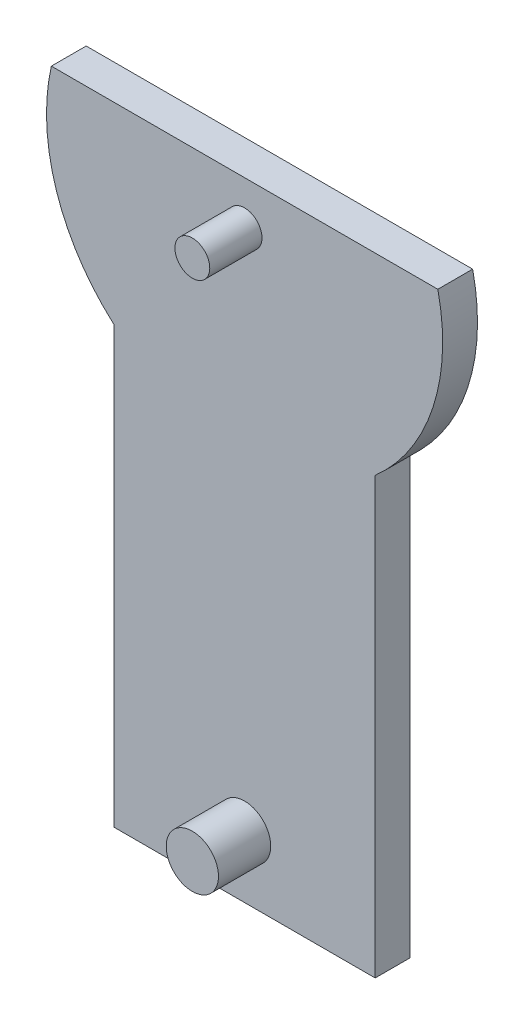
SolidWorks part; units mm, degrees
ref_plane "Front Plane" through (0, 0, 0) normal (0, 0, 1) x (1, 0, 0)
ref_plane "Top Plane" through (0, 0, 0) normal (0, 1, 0) x (1, 0, 0)
ref_plane "Right Plane" through (0, 0, 0) normal (1, 0, 0) x (0, 0, -1)
sketch "Sketch1" plane through (0, 0, 0) normal (0, 0, 1) x (1, 0, 0)
  line L0 (0, 150.6274) -> (0, -208.1955) construction
  line L1 (75, -335.5223) -> (75, -85.5223)
  line L2 (75, -335.5223) -> (-75, -335.5223)
  line L3 (-75, -335.5223) -> (-75, -85.5223)
  line L4 (-110.9687, 25) -> (110.9687, 25)
  arc A0 (-110.9687, 25) -> (110.9687, 25) centre (0, 0) ccw
  circle A1 centre (0, 0) radius 10
  point P10 (0, -335.5223)
  dimension "D1" = 227.5
  dimension "D2" = 20
  dimension "D3" = 25
  dimension "D4" = 250
  dimension "D5" = 150
extrude "Boss-Extrude1" add sketch "Sketch1" along normal blind 20 contours A0 L3 L2 L1 | L0 L4 A0 A1 | L4 L0 A1 A0 | L0 A1 | A1 L0 region at (50.6064, -35.5134, 0) region at (-50.6064, -35.5134, 0) region at (4.2441, 0, 0) region at (-4.2441, 0, 0) region at (0, -220.0462, 0)
extrude "Boss-Extrude2" add sketch "Sketch1<3>" along normal blind 30 from surface contours A1 starting at face at (0, -133.6618, 20)
sketch "Sketch1<3>" plane through (0, 0, 0) normal (0, 0, 1) x (1, 0, 0) same geometry as "Sketch1"
sketch "Sketch2" plane through (0, 0, 20) normal (0, 0, 1) x (1, 0, 0)
  circle A0 centre (0, -300) radius 15
  dimension "D2" = 30
  dimension "D1" = 300
extrude "Boss-Extrude3" add sketch "Sketch2" along normal blind 30
